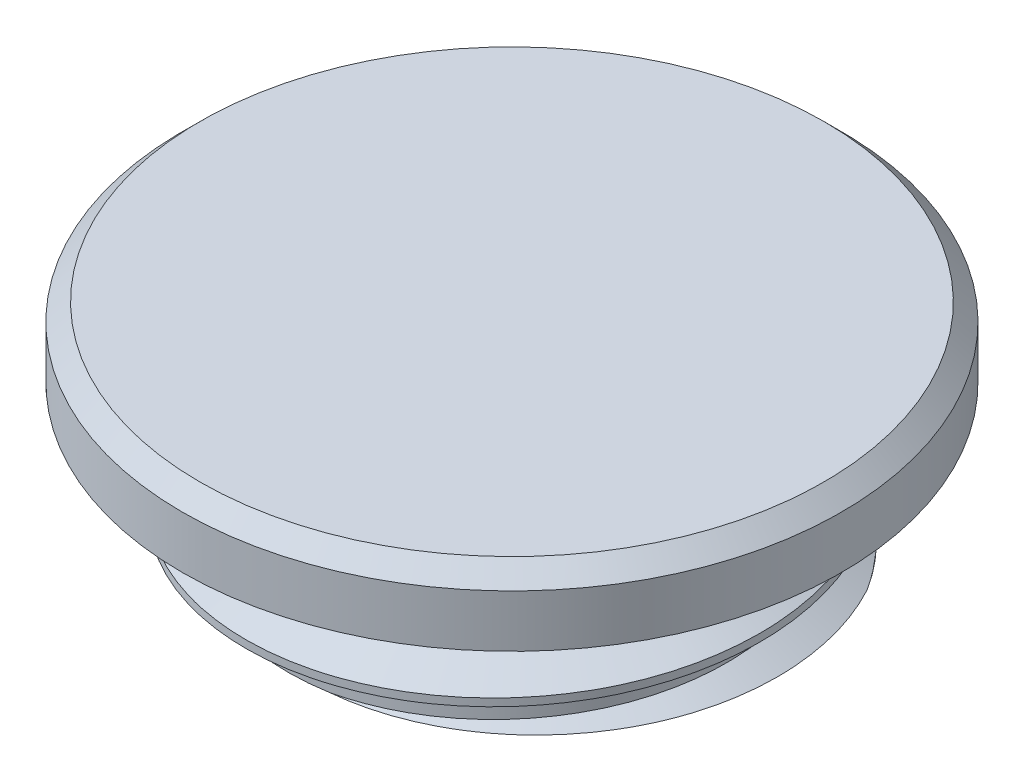
SolidWorks part; units mm, degrees
ref_plane "Front Plane" through (0, 0, 0) normal (0, 0, 1) x (1, 0, 0)
ref_plane "Top Plane" through (0, 0, 0) normal (0, 1, 0) x (1, 0, 0)
ref_plane "Right Plane" through (0, 0, 0) normal (1, 0, 0) x (0, 0, -1)
sketch "Sketch1" plane through (0, 0, 0) normal (0, 1, 0) x (1, 0, 0)
  circle A0 centre (0, 0) radius 14.75
  dimension "D1" = 29.5
extrude "Boss-Extrude1" add sketch "Sketch1" along normal blind 8
sketch "Sketch2" plane through (0, 8, 0) normal (0, 1, 0) x (1, 0, 0)
  circle A3 centre (-0.0051, -0.0315) radius 18.9
  dimension "D2" = 37.8
extrude "Boss-Extrude2" add sketch "Sketch2" along normal blind 4
thread "Thread1" pitch 3.5 start angle 0, offset 3.5, length 0, pitch 3.5, diameter 29.5
ref_plane "Plane1" through (-14.75, 11.5, 0) normal (0, 0, 1) x (-1, 0, 0)
sketch "Thread Profile1" plane through (-14.75, 11.5, 0) normal (0, 0, 1) x (-1, 0, 0)
  line L0 (0, 0) -> (0, 3.5) construction
  line L11 (0, 0) -> (0, 3.0625)
  line L12 (0, 3.0625) -> (-1.8944, 1.9687)
  line L13 (-1.8944, 1.9687) -> (-1.8944, 1.0937)
  line L15 (-1.8944, 1.0937) -> (0, 0)
  line L17 (-1.8944, 1.5312) -> (0, 1.5312) construction
  point P2 (0, 0)
  dimension "Pitch" = 3.5
  dimension "Profile_Angle" = 60
  dimension "Profile_Land" = 0.875
  dimension "Profile_Height" = 1.8944
chamfer "Chamfer2" distance 1 angle 45 1 edges at (-0.0051, 12, 18.9315)
sketch "Sketch3" plane through (0, 0, 0) normal (0, -1, 0) x (1, 0, 0)
  circle A0 centre (0, 0) radius 2
  dimension "D1" = 4
extrude "Cut-Extrude1" cut sketch "Sketch3" against normal blind 1
equation "\"ShaftDiameter\" = 29.5"
equation "\"D1@Sketch1\"=\"ShaftDiameter\""
equation "\"D6@Thread1\"=\"ThreadDia\""
